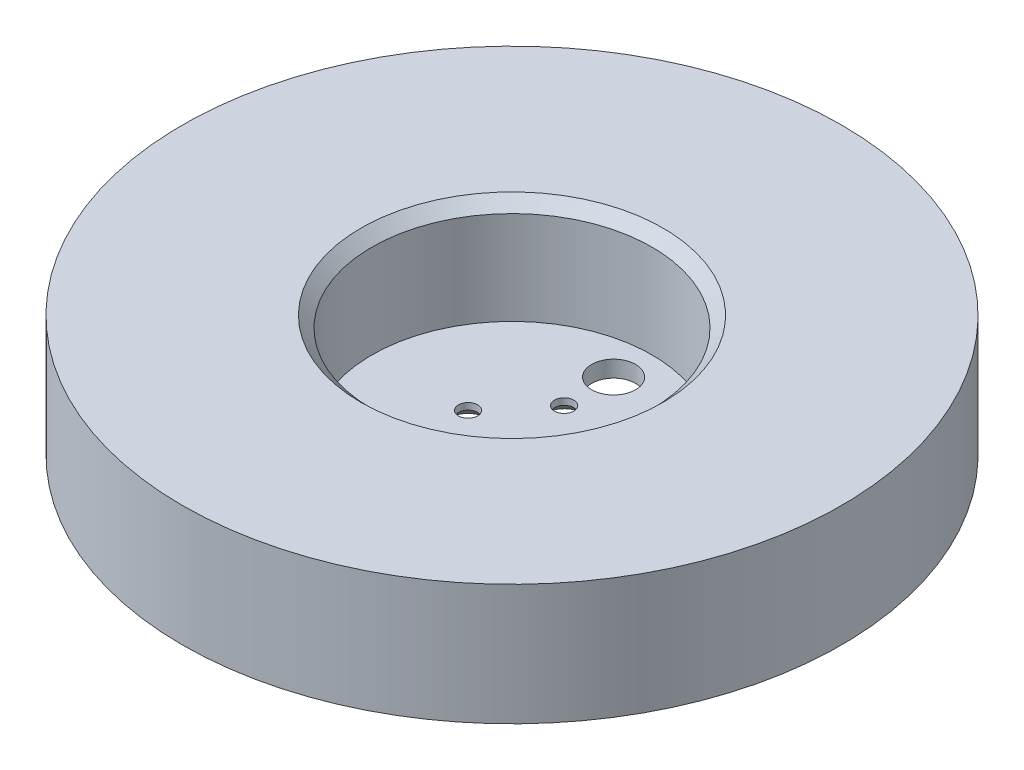
SolidWorks part; units mm, degrees
ref_plane "Front Plane" through (0, 0, 0) normal (0, 0, 1) x (1, 0, 0)
ref_plane "Top Plane" through (0, 0, 0) normal (0, 1, 0) x (1, 0, 0)
ref_plane "Right Plane" through (0, 0, 0) normal (1, 0, 0) x (0, 0, -1)
sketch "Sketch1" plane through (0, 0, 0) normal (0, 1, 0) x (1, 0, 0)
  circle A0 centre (0, 0) radius 60
  dimension "D1" = 120
extrude "Boss-Extrude1" add sketch "Sketch1" along normal blind 3
sketch "Sketch2" plane through (0, 3, 0) normal (0, 1, 0) x (1, 0, 0)
  circle A0 centre (0, 0) radius 25.5
  circle A2 centre (0, 0) radius 60
  circle A3 centre (0, 0) radius 60
  dimension "D1" = 0
  dimension "D2" = 51
extrude "Boss-Extrude2" add sketch "Sketch2" along normal blind 19
sketch "Sketch3" plane through (0, 0, 0) normal (0, -1, 0) x (1, 0, 0)
  circle A0 centre (0, 0) radius 55
  circle A1 centre (0, 0) radius 45
  dimension "D1" = 90
  dimension "D2" = 10
extrude "Cut-Extrude1" cut sketch "Sketch3" against normal blind 10
sketch "Sketch4" plane through (0, 3, 0) normal (0, 1, 0) x (1, 0, 0)
  circle A0 centre (0, 0) radius 9.5 construction
  circle A1 centre (0, 0) radius 8 construction
  circle A2 centre (0, 9.5) radius 1.75
  circle A4 centre (0, -9.5) radius 1.75
  circle A5 centre (-8, 0) radius 1.75
  circle A6 centre (8, 0) radius 1.75
  dimension "D1" = 19
  dimension "D2" = 3.5
  dimension "D3" = 16
extrude "Cut-Extrude2" cut sketch "Sketch4" against normal through all
chamfer "Chamfer1" distance 2 angle 45 1 edges at (0, 22, 25.5)
chamfer "Chamfer2" distance 1.8 angle 45 4 edges at (0, 0, -7.75) (-8, 0, 1.75) (8, 0, 1.75) (0, 0, 11.25)
sketch "Sketch5" plane through (0, 3, 0) normal (0, 1, 0) x (1, 0, 0)
  line L0 (0, 18.5) -> (0, 0) construction
  circle A0 centre (0, 0) radius 12.5 construction
  circle A1 centre (0, 18.5) radius 4
  dimension "D1" = 25
  dimension "D2" = 8
  dimension "D3" = 18.5
extrude "Cut-Extrude3" cut sketch "Sketch5" against normal through all
sketch "Sketch6" plane through (0, 0, 0) normal (0, -1, 0) x (1, 0, 0)
  line L0 (0, 0) -> (0, 45) construction
  circle A0 centre (0, 45) radius 5
  circle A1 centre (0, 0) radius 45 construction
  point P7 (0, 45)
  point P8 (0, 45.4468)
  dimension "D1" = 10
extrude "Cut-Extrude4" cut sketch "Sketch6" against normal up to surface (10 mm away) up to face at (0, 10, -45)
